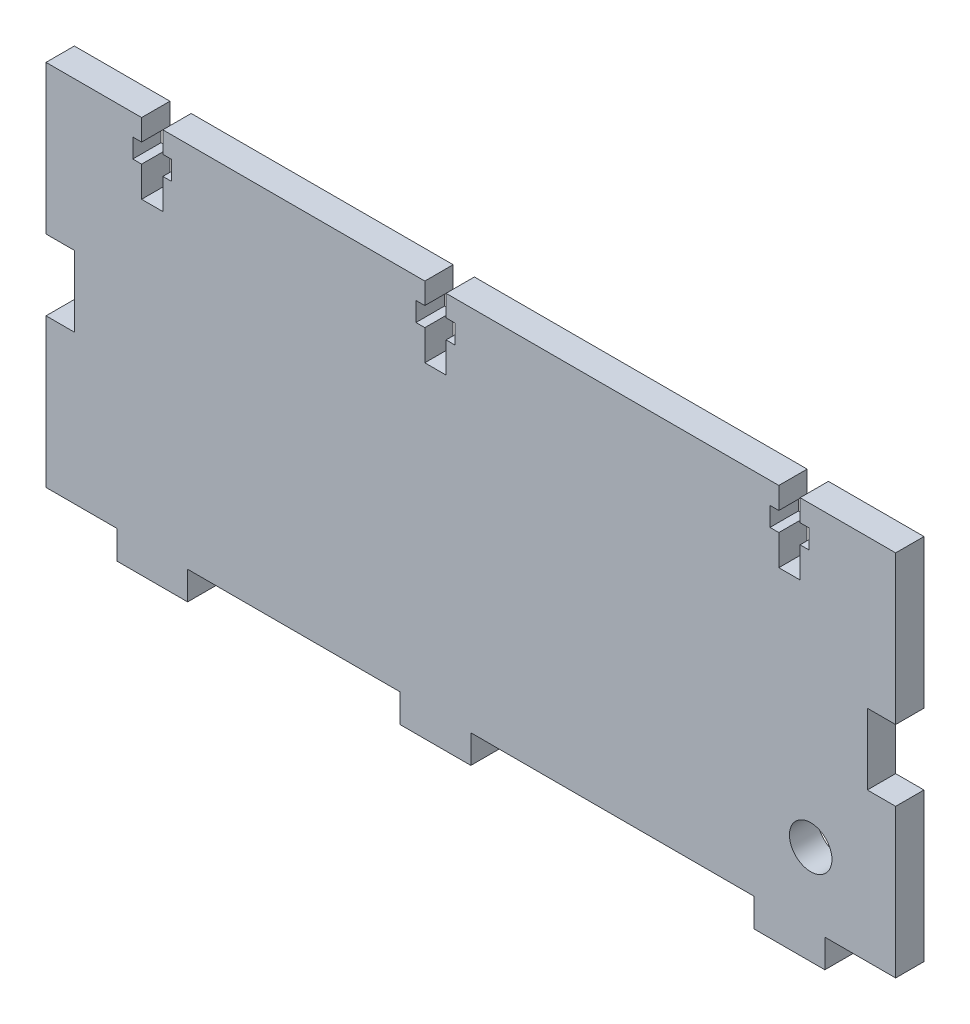
SolidWorks part; units mm, degrees
ref_plane "Front Plane" through (0, 0, 0) normal (0, 0, 1) x (1, 0, 0)
ref_plane "Top Plane" through (0, 0, 0) normal (0, 1, 0) x (1, 0, 0)
ref_plane "Right Plane" through (0, 0, 0) normal (1, 0, 0) x (0, 0, -1)
sketch "Sketch1" plane through (0, 0, 0) normal (0, 0, 1) x (1, 0, 0)
  line L0 (116, 26) -> (78.333, 26) construction
  line L1 (0, 0) -> (10, 0)
  line L2 (0, 0) -> (0, 21)
  line L3 (0, 52) -> (10, 52)
  line L4 (120, 0) -> (120, 21)
  line L5 (60, 0) -> (100, 0)
  line L6 (10, 0) -> (10, -4)
  line L7 (10, -4) -> (20, -4)
  line L8 (20, 0) -> (20, -4)
  line L9 (110, 0) -> (120, 0)
  line L10 (50, 0) -> (50, -4)
  line L11 (50, -4) -> (60, -4)
  line L12 (60, 0) -> (60, -4)
  line L13 (120, 31) -> (120, 52)
  line L14 (100, 0) -> (100, -4)
  line L15 (100, -4) -> (110, -4)
  line L16 (110, 0) -> (110, -4)
  line L17 (10, 52) -> (20, 52)
  line L18 (110, 52) -> (120, 52)
  line L19 (120, 21) -> (116, 21)
  line L20 (120, 21) -> (120, 31)
  line L21 (120, 31) -> (116, 31)
  line L22 (20, 0) -> (50, 0)
  line L23 (116, 21) -> (116, 31)
  line L24 (50, 52) -> (60, 52)
  line L28 (60, 52) -> (100, 52)
  line L32 (108, 10) -> (0, 24.4568) construction
  line L36 (100, 52) -> (110, 52)
  line L37 (0, 31) -> (0, 52)
  line L38 (20, 52) -> (50, 52)
  line L39 (0, 21) -> (4, 21)
  line L40 (0, 21) -> (0, 31)
  line L41 (0, 31) -> (4, 31)
  line L42 (4, 21) -> (4, 31)
  circle A0 centre (108, 10) radius 3
  circle A1 centre (23.1929, 38) radius 10 construction
  point P22 (5, 0)
  dimension "D10" = 20
  dimension "D13" = 6
  dimension "D15" = 12
  dimension "D1" = 120
  dimension "D2" = 52
  dimension "D3" = 4
  dimension "D4" = 10
  dimension "D5" = 10
  dimension "D6" = 4
  dimension "D7" = 21
  dimension "D8" = 10
  dimension "D9" = 30
  dimension "D11" = 14
  dimension "D14" = 10
  dimension "D16" = 21
extrude "Boss-Extrude1" add sketch "Sketch1" along normal blind 4 contours L42 L39 L2 L1 L6 L7 L8 L22 L10 L11 L12 L5 L14 L15 L16 L9 L4 L19 L23 L21 L13 L18 L28 L38 L3 L37 L41 A0 region at (59.7509, 25.5349, 0)
sketch "Sketch2" plane through (0, 0, 4) normal (0, 0, 1) x (1, 0, 0)
  line L0 (0, 52) -> (120, 52) construction
  line L1 (13.5, 52) -> (16.5, 52)
  line L2 (13.5, 52) -> (13.5, 49)
  line L3 (13.5, 42) -> (16.5, 42)
  line L4 (16.5, 52) -> (16.5, 49)
  line L5 (15, 42) -> (15, 52) construction
  line L6 (12.25, 46.3) -> (13.5, 46.3)
  line L7 (12.25, 46.3) -> (12.25, 49)
  line L8 (12.25, 49) -> (13.5, 49)
  line L9 (17.75, 46.3) -> (17.75, 49)
  line L10 (12.25, 46.3) -> (17.75, 49) construction
  line L11 (12.25, 49) -> (17.75, 46.3) construction
  line L12 (16.5, 46.3) -> (17.75, 46.3)
  line L13 (16.5, 46.3) -> (16.5, 42)
  line L14 (16.5, 49) -> (17.75, 49)
  line L15 (13.5, 46.3) -> (13.5, 42)
  line L16 (53.5, 52) -> (56.5, 52)
  line L17 (53.5, 52) -> (53.5, 49)
  line L18 (53.5, 42) -> (56.5, 42)
  line L19 (56.5, 52) -> (56.5, 49)
  line L20 (55, 42) -> (55, 52) construction
  line L21 (52.25, 46.3) -> (53.5, 46.3)
  line L22 (52.25, 46.3) -> (52.25, 49)
  line L23 (52.25, 49) -> (53.5, 49)
  line L24 (57.75, 46.3) -> (57.75, 49)
  line L25 (52.25, 46.3) -> (57.75, 49) construction
  line L26 (52.25, 49) -> (57.75, 46.3) construction
  line L27 (56.5, 46.3) -> (57.75, 46.3)
  line L28 (56.5, 46.3) -> (56.5, 42)
  line L29 (56.5, 49) -> (57.75, 49)
  line L30 (53.5, 46.3) -> (53.5, 42)
  line L31 (103.5, 52) -> (106.5, 52)
  line L32 (103.5, 52) -> (103.5, 48.9372)
  line L33 (103.5, 41.9372) -> (106.5, 41.9372)
  line L34 (106.5, 52) -> (106.5, 48.9372)
  line L35 (105, 41.9372) -> (105, 52) construction
  line L36 (102.25, 46.2372) -> (103.5, 46.2372)
  line L37 (102.25, 46.2372) -> (102.25, 48.9372)
  line L38 (102.25, 48.9372) -> (103.5, 48.9372)
  line L39 (107.75, 46.2372) -> (107.75, 48.9372)
  line L40 (102.25, 46.2372) -> (107.75, 48.9372) construction
  line L41 (102.25, 48.9372) -> (107.75, 46.2372) construction
  line L42 (106.5, 46.2372) -> (107.75, 46.2372)
  line L43 (106.5, 46.2372) -> (106.5, 41.9372)
  line L44 (106.5, 48.9372) -> (107.75, 48.9372)
  line L45 (103.5, 46.2372) -> (103.5, 41.9372)
  line L46 (0, 31) -> (0, 52) construction
  line L47 (120, 31) -> (120, 52) construction
  point P6 (15, 47.65)
  point P21 (55, 47.65)
  point P36 (105, 47.5872)
  point P51 (0, 0)
  dimension "D1" = 10
  dimension "D2" = 3
  dimension "D3" = 3
  dimension "D4" = 2.7
  dimension "D5" = 5.5
  dimension "D6" = 3
  dimension "D7" = 2.7
  dimension "D8" = 3
  dimension "D9" = 2.7
  dimension "D10" = 3
  dimension "D11" = 10
  dimension "D12" = 55
  dimension "D13" = 15
  dimension "D14" = 15
extrude "Cut-Extrude1" cut sketch "Sketch2" against normal blind 4
